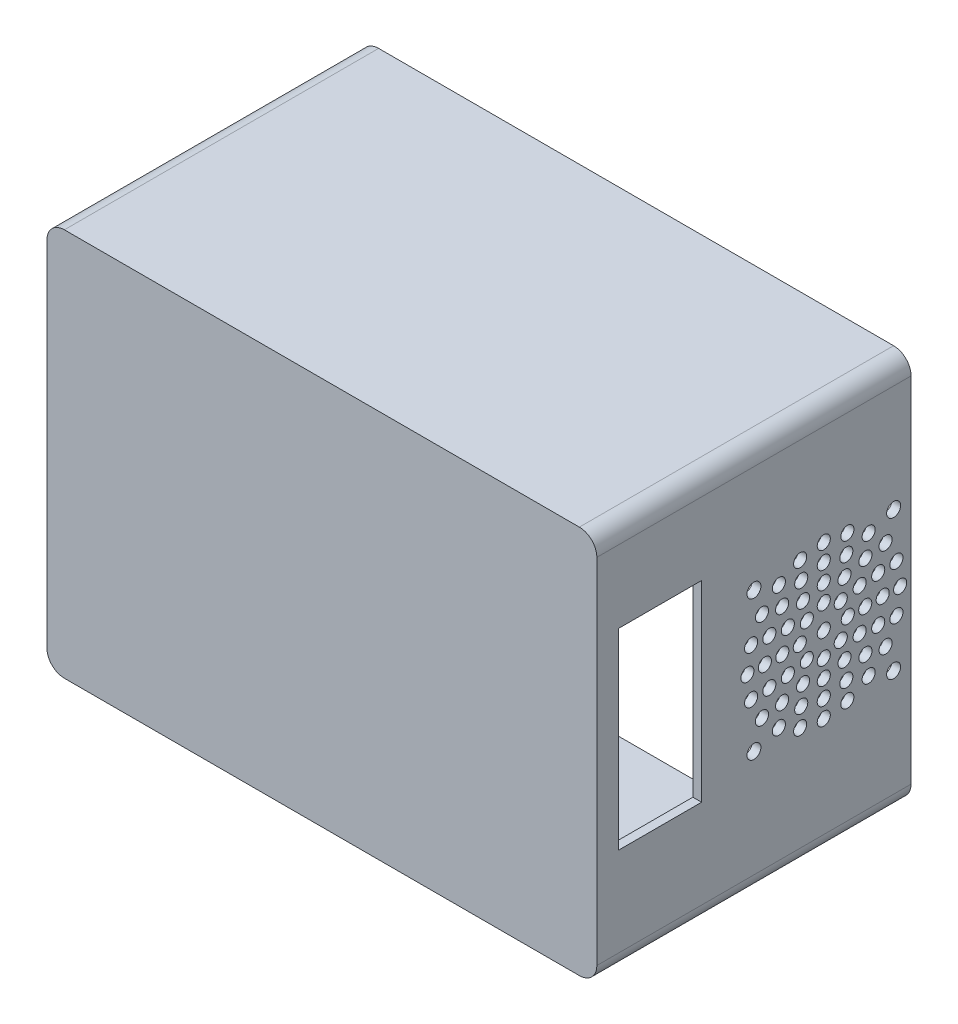
SolidWorks part; units mm, degrees
ref_plane "前视基准面" through (0, 0, 0) normal (0, 0, 1) x (1, 0, 0)
ref_plane "上视基准面" through (0, 0, 0) normal (0, 1, 0) x (1, 0, 0)
ref_plane "右视基准面" through (0, 0, 0) normal (1, 0, 0) x (0, 0, -1)
other "Configuration Table"
sketch "草图1" plane through (0, 0, 0) normal (0, 0, 1) x (1, 0, 0)
  line L0 (-4, 42.5) -> (-4, 36.5)
  line L1 (-61, 42.5) -> (61, 42.5)
  line L2 (-61, 42.5) -> (-61, -42.5)
  line L3 (-61, -42.5) -> (61, -42.5)
  line L4 (61, 42.5) -> (61, -42.5)
  line L5 (0, -42.5) -> (0, 42.5) construction
  line L6 (-61, 0) -> (61, 0) construction
  line L7 (-63, 44.5) -> (63, 44.5)
  line L8 (-63, 44.5) -> (-63, -44.5)
  line L9 (-63, -44.5) -> (63, -44.5)
  line L10 (63, 44.5) -> (63, -44.5)
  line L11 (0, -44.5) -> (0, 44.5) construction
  line L12 (-63, 0) -> (63, 0) construction
  line L13 (-4, 36.5) -> (4, 36.5)
  line L14 (4, 36.5) -> (4, 42.5)
  line L15 (55, 42.5) -> (55, 36.5)
  line L16 (55, 36.5) -> (61, 36.5)
  line L17 (-61, -36.5) -> (-55, -36.5)
  line L18 (-55, -36.5) -> (-55, -42.5)
  line L19 (-4, -42.5) -> (-4, -36.5)
  line L20 (-4, -36.5) -> (4, -36.5)
  line L21 (4, -36.5) -> (4, -42.5)
  line L22 (61, -36.5) -> (55, -36.5)
  line L23 (55, -36.5) -> (55, -42.5)
  line L24 (-55, 42.5) -> (-55, 36.5)
  line L25 (-55, 36.5) -> (-61, 36.5)
  circle A0 centre (0, 40.5) radius 2.15
  circle A2 centre (-59, 40.5) radius 2.15
  circle A3 centre (59, 40.5) radius 2.15
  circle A5 centre (-59, -40.5) radius 2
  circle A6 centre (0, -40.5) radius 2.15
  circle A7 centre (59, -40.5) radius 2.15
  point P0 (0, 0)
  point P4 (0, 0)
  dimension "D8" = 4.3
  dimension "D9" = 4
  dimension "D12" = 4.3
  dimension "D13" = 4
  dimension "D14" = 4
  dimension "D17" = 4.3
  dimension "D18" = 4
  dimension "D19" = 4
  dimension "D22" = 4
  dimension "D23" = 4
  dimension "D24" = 4
  dimension "D25" = 4.3
  dimension "D29" = 4
  dimension "D30" = 4.3
  dimension "D31" = 4
  dimension "D32" = 4
  dimension "D1" = 122
  dimension "D2" = 85
  dimension "D3" = 2
  dimension "D4" = 2
  dimension "D5" = 8
  dimension "D6" = 4
  dimension "D7" = 8
  dimension "D10" = 8
  dimension "D11" = 8
  dimension "D15" = 8
  dimension "D16" = 8
  dimension "D20" = 8
  dimension "D21" = 8
  dimension "D26" = 8
  dimension "D27" = 4
  dimension "D28" = 8
extrude "凸台-拉伸4" add sketch "草图1" along normal blind 70 contours L10 L7 L8 L9 A7 L3 A6 L2 A2 L1 A0 A3 L4 | A5 L3 L18 L17 L2 | A6 L3 L21 L20 L19 | A7 L4 L22 L23 L3 | A3 L1 L15 L16 L4 | A0 L1 L0 L13 L14 | A2 L2 L25 L24 L1 | A5 L2 L3 | A7 L3 L4 | A3 L4 L1 | A2 L1 L2 region at (-2.3945, 42.4, 0) region at (-57.2815, 38.7815, 0) region at (-60.655, 42.155, 0) region at (57.2815, 38.7815, 0) region at (-57.3463, -38.8463, 0) region at (-60.5533, -42.0533, 0) region at (60.655, 42.155, 0) region at (57.2815, -38.7815, 0) region at (-3.9, -39.5, 0) region at (60.655, -42.155, 0) region at (0, 42.9574, 0)
sketch "草图3" plane through (0, 0, 70) normal (0, 0, 1) x (1, 0, 0)
  line L1 (-63, 44.5) -> (63, 44.5)
  line L2 (-63, 44.5) -> (-63, -44.5)
  line L3 (-63, -44.5) -> (63, -44.5)
  line L4 (63, 44.5) -> (63, -44.5)
extrude "凸台-拉伸5" add sketch "草图3" along normal blind 2
sketch "草图4" plane through (63, 0, 0) normal (1, 0, 0) x (0, 0, -1)
  line L0 (-20, 19) -> (-20, 0) construction
  line L5 (0, 44.5) -> (0, -44.5) construction
  line L7 (0, 20) -> (-40, 20) construction
  line L8 (0, 20) -> (0, -20) construction
  line L9 (0, -20) -> (-40, -20) construction
  line L10 (-40, 20) -> (-40, -20) construction
  circle A0 centre (-20, 0) radius 19 construction
  circle A1 centre (-36, 16) radius 1.6
  circle A2 centre (-4, 16) radius 1.6
  circle A3 centre (-4, -16) radius 1.6
  circle A4 centre (-36, -16) radius 1.6
  circle A5 centre (-20, 17.5) radius 1.5
  circle A6 centre (-20, 0) radius 1.5
  circle A7 centre (-20, 9.5) radius 1.5
  circle A8 centre (-20, 13.5) radius 1.5
  circle A9 centre (-20, 5.5) radius 1.5
  circle A10 centre (-14.5922, 16.6435) radius 1.5
  circle A11 centre (-9.7138, 14.1578) radius 1.5
  circle A12 centre (-5.8422, 10.2862) radius 1.5
  circle A13 centre (-3.3565, 5.4078) radius 1.5
  circle A14 centre (-2.5, 0) radius 1.5
  circle A15 centre (-3.3565, -5.4078) radius 1.5
  circle A16 centre (-5.8422, -10.2862) radius 1.5
  circle A17 centre (-9.7138, -14.1578) radius 1.5
  circle A18 centre (-14.5922, -16.6435) radius 1.5
  circle A19 centre (-20, -17.5) radius 1.5
  circle A20 centre (-25.4078, -16.6435) radius 1.5
  circle A21 centre (-30.2862, -14.1578) radius 1.5
  circle A22 centre (-34.1578, -10.2862) radius 1.5
  circle A23 centre (-36.6435, -5.4078) radius 1.5
  circle A24 centre (-37.5, 0) radius 1.5
  circle A25 centre (-36.6435, 5.4078) radius 1.5
  circle A26 centre (-34.1578, 10.2862) radius 1.5
  circle A27 centre (-30.2862, 14.1578) radius 1.5
  circle A28 centre (-25.4078, 16.6435) radius 1.5
  circle A29 centre (-14.8338, 12.4724) radius 1.5
  circle A30 centre (-10.4541, 9.5459) radius 1.5
  circle A31 centre (-7.5276, 5.1662) radius 1.5
  circle A32 centre (-6.5, 0) radius 1.5
  circle A33 centre (-7.5276, -5.1662) radius 1.5
  circle A34 centre (-10.4541, -9.5459) radius 1.5
  circle A35 centre (-14.8338, -12.4724) radius 1.5
  circle A36 centre (-20, -13.5) radius 1.5
  circle A37 centre (-25.1662, -12.4724) radius 1.5
  circle A38 centre (-29.5459, -9.5459) radius 1.5
  circle A39 centre (-32.4724, -5.1662) radius 1.5
  circle A40 centre (-33.5, 0) radius 1.5
  circle A41 centre (-32.4724, 5.1662) radius 1.5
  circle A42 centre (-29.5459, 9.5459) radius 1.5
  circle A43 centre (-25.1662, 12.4724) radius 1.5
  circle A44 centre (-15.25, 8.2272) radius 1.5
  circle A45 centre (-11.7728, 4.75) radius 1.5
  circle A46 centre (-10.5, 0) radius 1.5
  circle A47 centre (-11.7728, -4.75) radius 1.5
  circle A48 centre (-15.25, -8.2272) radius 1.5
  circle A49 centre (-20, -9.5) radius 1.5
  circle A50 centre (-24.75, -8.2272) radius 1.5
  circle A51 centre (-28.2272, -4.75) radius 1.5
  circle A52 centre (-29.5, 0) radius 1.5
  circle A53 centre (-28.2272, 4.75) radius 1.5
  circle A54 centre (-24.75, 8.2272) radius 1.5
  circle A55 centre (-16.1109, 3.8891) radius 1.5
  circle A56 centre (-14.5, 0) radius 1.5
  circle A57 centre (-16.1109, -3.8891) radius 1.5
  circle A58 centre (-20, -5.5) radius 1.5
  circle A59 centre (-23.8891, -3.8891) radius 1.5
  circle A60 centre (-25.5, 0) radius 1.5
  circle A61 centre (-23.8891, 3.8891) radius 1.5
  point P68 (-20, 0)
  point P100 (-20, 0)
  point P122 (-20, 0)
  point P138 (-20, 0)
  dimension "D1" = 38
  dimension "D5" = 4
  dimension "D6" = 4
  dimension "D7" = 3.2
  dimension "D10" = 20
  dimension "D11" = 20
  dimension "D12" = 3
  dimension "D13" = 3
  dimension "D14" = 3
  dimension "D15" = 9.5
  dimension "D16" = 8
  dimension "D17" = 3
  dimension "D18" = 3
  dimension "D19" = 4
  dimension "D20" = 4
  dimension "D2" = 40
  dimension "D3" = 40
  dimension "D4" = 20
  dimension "D8" = 2
  dimension "D9" = 2
  dimension "D21" = 20
  dimension "D22" = 16
  dimension "D23" = 12
  dimension "D24" = 8
extrude "切除-拉伸1" cut sketch "草图4" against normal blind 3 contours A1 | A3 | A4 | A42 | A27 | A28 | A5 | A10 | A29 | A11 | A8 | A43 | A26 | A25 | A41 | A53 | A54 | A7 | A22 | A38 | A21 | A37 | A20 | A19 | A23 | A24 | A40 | A39 | A52 | A60 | A61 | A9 | A44 | A30 | A12 | A13 | A14 | A15 | A16 | A17 | A18 | A35 | A36 | A34 | A33 | A32 | A31 | A45 | A46 | A56 | A55 | A6 | A59 | A51 | A58 | A57 | A47 | A48 | A49 | A50 | A2
sketch "草图6" plane through (-63, 0, 0) normal (-1, 0, 0) x (0, 0, 1)
  line L0 (72, 44.5) -> (0, 44.5) construction
  line L1 (0, 44.5) -> (0, -44.5) construction
  circle A0 centre (10, 34.5) radius 1.6
  circle A1 centre (20, 34.5) radius 1.6
  circle A2 centre (30, 34.5) radius 1.6
  circle A6 centre (20, 26) radius 1.6
  circle A7 centre (30, 26) radius 1.6
  circle A11 centre (20, 17.5) radius 1.6
  circle A12 centre (30, 17.5) radius 1.6
  circle A16 centre (20, 9) radius 1.6
  circle A17 centre (30, 9) radius 1.6
  circle A21 centre (20, 0.5) radius 1.6
  circle A22 centre (30, 0.5) radius 1.6
  circle A26 centre (20, -8) radius 1.6
  circle A27 centre (30, -8) radius 1.6
  circle A31 centre (20, -16.5) radius 1.6
  circle A32 centre (30, -16.5) radius 1.6
  circle A36 centre (20, -25) radius 1.6
  circle A37 centre (30, -25) radius 1.6
  circle A41 centre (20, -33.5) radius 1.6
  circle A42 centre (30, -33.5) radius 1.6
  circle A46 centre (10, 26) radius 1.6
  circle A47 centre (10, 17.5) radius 1.6
  circle A48 centre (10, 9) radius 1.6
  circle A49 centre (10, 0.5) radius 1.6
  circle A50 centre (10, -8) radius 1.6
  circle A51 centre (10, -16.5) radius 1.6
  circle A52 centre (10, -25) radius 1.6
  circle A53 centre (10, -33.5) radius 1.6
  circle A54 centre (40, 34.5) radius 1.6 [skipped]
  circle A55 centre (50, 34.5) radius 1.6 [skipped]
  circle A56 centre (60, 34.5) radius 1.6 [skipped]
  circle A57 centre (40, 26) radius 1.6 [skipped]
  circle A58 centre (50, 26) radius 1.6 [skipped]
  circle A59 centre (60, 26) radius 1.6 [skipped]
  circle A60 centre (40, 17.5) radius 1.6 [skipped]
  circle A61 centre (50, 17.5) radius 1.6 [skipped]
  circle A62 centre (60, 17.5) radius 1.6 [skipped]
  circle A63 centre (40, 9) radius 1.6 [skipped]
  circle A64 centre (50, 9) radius 1.6 [skipped]
  circle A65 centre (60, 9) radius 1.6 [skipped]
  circle A66 centre (40, 0.5) radius 1.6 [skipped]
  circle A67 centre (50, 0.5) radius 1.6 [skipped]
  circle A68 centre (60, 0.5) radius 1.6 [skipped]
  circle A69 centre (40, -8) radius 1.6 [skipped]
  circle A70 centre (50, -8) radius 1.6 [skipped]
  circle A71 centre (60, -8) radius 1.6 [skipped]
  circle A72 centre (40, -16.5) radius 1.6 [skipped]
  circle A73 centre (50, -16.5) radius 1.6 [skipped]
  circle A74 centre (60, -16.5) radius 1.6 [skipped]
  circle A75 centre (40, -25) radius 1.6 [skipped]
  circle A76 centre (50, -25) radius 1.6 [skipped]
  circle A77 centre (60, -25) radius 1.6 [skipped]
  circle A78 centre (40, -33.5) radius 1.6 [skipped]
  circle A79 centre (50, -33.5) radius 1.6 [skipped]
  circle A80 centre (60, -33.5) radius 1.6 [skipped]
  dimension "D1" = 3.2
  dimension "D2" = 10
  dimension "D3" = 10
  dimension "D4" = 6
  dimension "D5" = 9
extrude "切除-拉伸3" cut sketch "草图6" against normal blind 2
sketch "草图8" plane through (0, -44.5, 0) normal (0, -1, 0) x (1, 0, 0)
  line L0 (-63, 0) -> (63, 0) construction
  line L1 (-55, 0) -> (55, 0)
  line L2 (-55, 0) -> (-55, 22)
  line L3 (-55, 22) -> (55, 22)
  line L4 (55, 0) -> (55, 22)
  line L5 (-63, 72) -> (-63, 0) construction
  line L6 (63, 72) -> (63, 0) construction
  line L7 (-63, 72) -> (63, 72) construction
  dimension "D1" = 8
  dimension "D2" = 8
  dimension "D3" = 50
extrude "切除-拉伸4" cut sketch "草图8" against normal blind 8
fillet "圆角3" radius 4 12 edges at (-55, 36.5, 35) (-55, -36.5, 35) (-63, 44.5, 36) (-63, -44.5, 36) (4, -36.5, 46) (-4, -36.5, 46) (4, 36.5, 35) (-4, 36.5, 35) (55, -36.5, 35) (63, -44.5, 36) (63, 44.5, 36) (55, 36.5, 35)
sketch "草图9" plane through (61, 0, 0) normal (-1, 0, 0) x (0, 0, 1)
  line L0 (70, 36.5) -> (70, -36.5) construction
  line L5 (70, 32.4074) -> (45.8, 32.4074) construction
  line L6 (70, 32.4074) -> (70, -32.5926) construction
  line L7 (70, -32.5926) -> (45.8, -32.5926) construction
  line L8 (45.8, 32.4074) -> (45.8, -32.5926) construction
  line L10 (48, 23.9074) -> (67, 23.9074)
  line L11 (48, 23.9074) -> (48, -20.0926)
  line L12 (48, -20.0926) -> (67, -20.0926)
  line L13 (67, 23.9074) -> (67, -20.0926)
  dimension "D1" = 65
  dimension "D2" = 24.2
  dimension "D3" = 44
  dimension "D4" = 19
  dimension "D5" = 3
  dimension "D6" = 8.5
extrude "切除-拉伸5" cut sketch "草图9" against normal blind 2
sketch "草图10" plane through (0, 0, 22) normal (0, 0, -1) x (-1, 0, 0)
  line L0 (-55, -44.5) -> (55, -44.5) construction
  line L1 (-55, -42.5) -> (-43, -42.5)
  line L2 (-55, -42.5) -> (-55, -44.5)
  line L3 (-55, -44.5) -> (-43, -44.5)
  line L4 (-43, -42.5) -> (-43, -44.5)
  dimension "D1" = 12
extrude "凸台-拉伸6" add sketch "草图10" along normal up to surface (22 mm away) up to face at (61.15, -40.5, 0)
